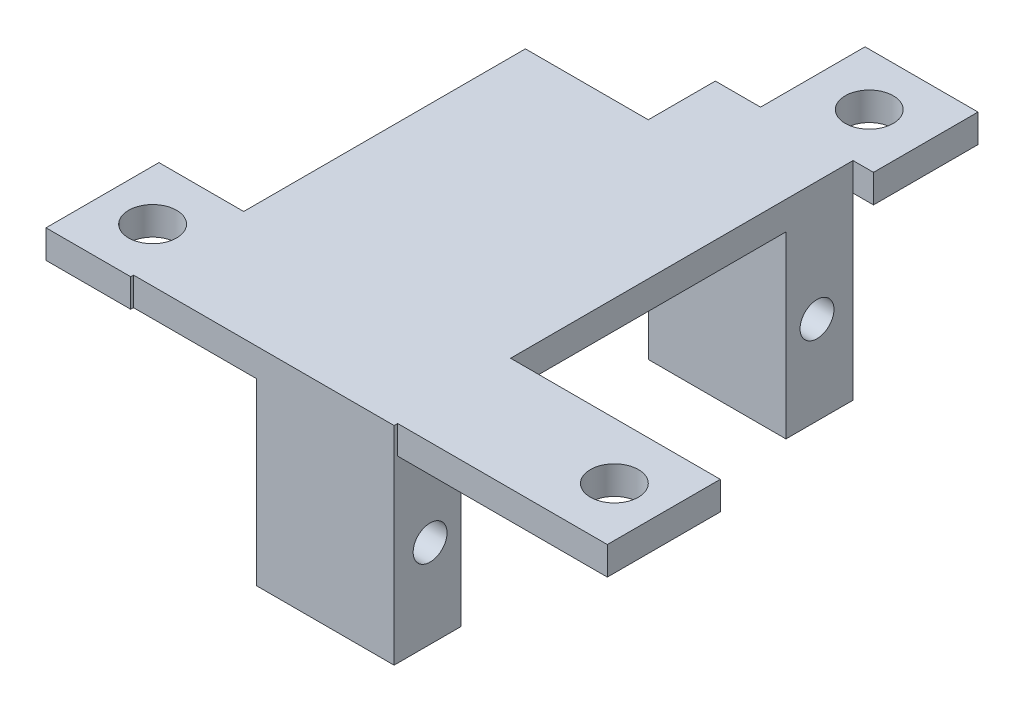
SolidWorks part; units mm, degrees
note: The reader was unsure of these and kept them because the rebuilt part matched: shared geometry of "Sketch1<5>", "Sketch1<6>".
ref_plane "Front Plane" through (0, 0, 0) normal (0, 0, 1) x (1, 0, 0)
ref_plane "Top Plane" through (0, 0, 0) normal (0, 1, 0) x (1, 0, 0)
ref_plane "Right Plane" through (0, 0, 0) normal (1, 0, 0) x (0, 0, -1)
sketch "Sketch1" plane through (0, 0, 0) normal (0, 1, 0) x (1, 0, 0)
  line L0 (0.95, 16.25) -> (0.95, 11.5)
  line L1 (-17.5, -16.25) -> (17.5, -16.25)
  line L2 (-17.5, -16.25) -> (-17.5, 16.25)
  line L3 (-17.5, 16.25) -> (17.5, 16.25)
  line L4 (17.5, -16.25) -> (17.5, 16.25)
  line L5 (-17.5, -16.25) -> (17.5, 16.25) construction
  line L6 (-17.5, 16.25) -> (17.5, -16.25) construction
  line L7 (0.95, 11.5) -> (-17.5, 11.5)
  line L8 (0.95, -16.25) -> (0.95, -11.5)
  line L9 (0.95, -11.5) -> (-17.5, -11.5)
  line L10 (0.95, 11.5) -> (0.95, -11.5)
  line L11 (-8.8, 16.25) -> (-8.8, 11.5)
  line L12 (0.95, -8) -> (15.8, -8)
  line L13 (15.8, -8) -> (15.8, -16)
  line L14 (15.8, -16) -> (0.95, -16)
  line L15 (-5.6, 16.25) -> (-5.6, 23.65)
  line L16 (-5.6, 23.65) -> (2.4, 23.65)
  line L17 (2.4, 23.65) -> (2.4, 16.25)
  line L18 (-17.5, -16.45) -> (-23.5, -16.45)
  line L19 (-23.5, -16.45) -> (-23.5, -8.45)
  line L20 (-23.5, -8.45) -> (-17.5, -8.45)
  line L21 (-17.5, -16.45) -> (-17.5, -8.45)
  line L22 (-8.8, -11.5) -> (-8.8, -16.25)
  circle A0 centre (12.3, -12) radius 1.7
  circle A1 centre (-1.6, 19.95) radius 1.7
  circle A2 centre (-19.95, -12.45) radius 1.7
  point P0 (0, 0)
  point P11 (0.95, 0)
  point P36 (15.8, -12)
  point P39 (-23.5, -12.45)
  point P41 (2.4, 19.95)
  point P42 (-1.6, 23.65)
  dimension "D6" = 3.4
  dimension "D7" = 3.4
  dimension "D8" = 3.4
  dimension "D1" = 32.5
  dimension "D2" = 23
  dimension "D3" = 8.7
  dimension "D4" = 18.45
  dimension "D5" = 16.55
  dimension "D9" = 12.3
  dimension "D10" = 12
  dimension "D11" = 8
  dimension "D12" = 12.45
  dimension "D13" = 8
  dimension "D14" = 19.95
  dimension "D15" = 8
  dimension "D16" = 1.6
  dimension "D17" = 19.95
  dimension "D18" = 15.8
  dimension "D19" = 6
extrude "Boss-Extrude1" add sketch "Sketch1" along normal blind 2 contours L18 L21 L2 L20 L19 A2 | A2 | L10 L7 L2 L9 | L8 L9 L2 L1 | L3 L11 L7 L0 | A1 | L17 L16 L15 L3 A1 | A0 | L14 L13 L12 L10 A0 | L22 L9 L2 L1
extrude "Boss-Extrude2" add sketch "Sketch1<5>" against normal blind 12.7 from surface at 0 contours L3 L11 L7 L0 | L8 L9 L2 L1
sketch "Sketch1<5>" plane through (0, 0, 0) normal (0, 1, 0) x (1, 0, 0) same geometry as "Sketch1"
extrude "Cut-Extrude1" cut sketch "Sketch1<6>" against normal through all both and the other way through all contours A1 | A0 | A2
sketch "Sketch1<6>" plane through (0, 0, 0) normal (0, 1, 0) x (1, 0, 0) same geometry as "Sketch1"
sketch "Sketch2" plane through (0, 0, 0) normal (1, 0, 0) x (0, 0, -1)
  line L0 (13.7, -6.45) -> (-13.7, -6.45) construction
  circle A0 centre (-13.7, -6.45) radius 1.2
  circle A1 centre (13.7, -6.45) radius 1.2
  point P4 (0, -6.45)
  dimension "D1" = 2.4
  dimension "D2" = 2.4
  dimension "D3" = 27.4
  dimension "D4" = 6.45
extrude "Cut-Extrude2" cut sketch "Sketch2" against normal blind 8 from surface at 0.95 starting at face at (0.95, -3.5667, 14.5833)
